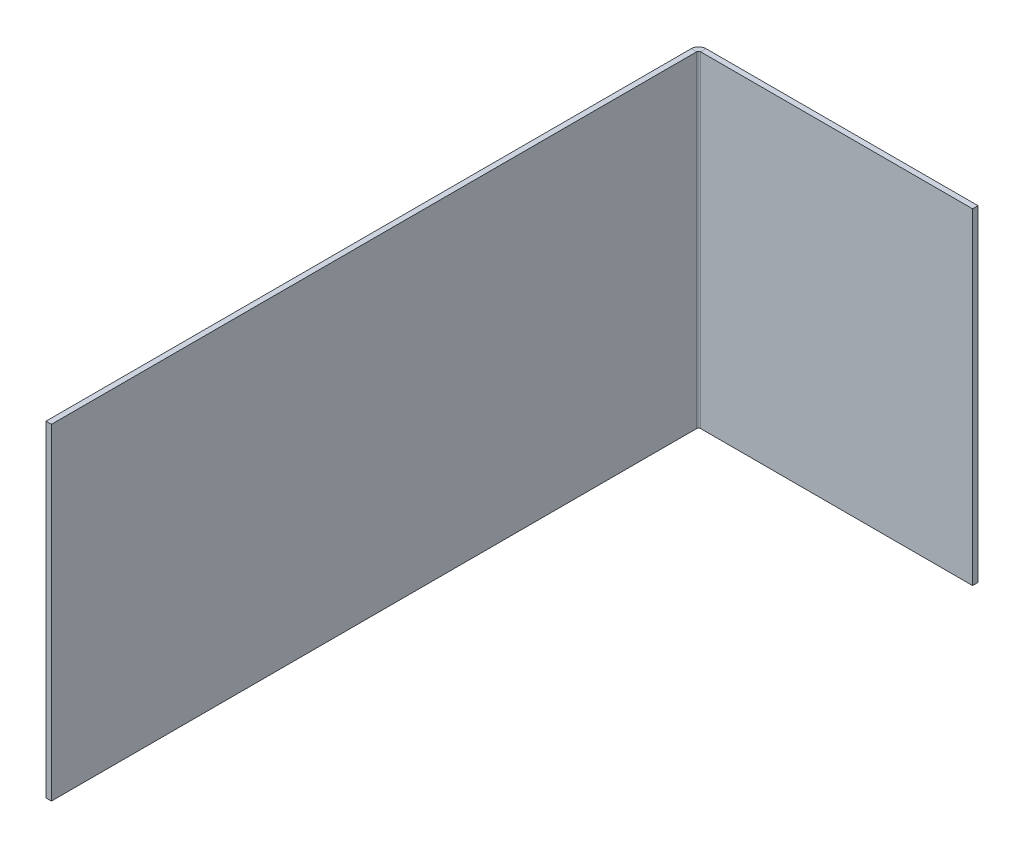
SolidWorks part; units mm, degrees
note: The reader was unsure of these and kept them because the rebuilt part matched: flange length of "Edge-Flange1".
material "1.0037 (S235JR)"
ref_plane "Front Plane" through (0, 0, 0) normal (0, 0, 1) x (1, 0, 0)
ref_plane "Top Plane" through (0, 0, 0) normal (0, 1, 0) x (1, 0, 0)
ref_plane "Right Plane" through (0, 0, 0) normal (1, 0, 0) x (0, 0, -1)
sketch "Sketch2" plane through (0, 0, 0) normal (0, 0, 1) x (1, 0, 0)
  line L1 (-50, 60) -> (50, 60)
  line L2 (-50, 60) -> (-50, -60)
  line L3 (-50, -60) -> (50, -60)
  line L4 (50, 60) -> (50, -60)
  line L5 (-50, 60) -> (50, -60) construction
  line L6 (-50, -60) -> (50, 60) construction
  point P0 (0, 0)
  dimension "D1" = 100
  dimension "D2" = 120
base flange "Base-Flange1" sketch "Sketch2" thickness 2 reverse thickness direction no parameters "D1"=0.7366
edge flange "Edge-Flange1" sketch "Sketch9" flange angle 90 flange length 240 flange position bend outside bend radius 0.7366 thickness 2 relief rectangular parameters "D6"=10
sketch "Sketch9" plane through (-50, 0, 0) normal (1, 0, 0) x (0, 1, 0)
  line L2 (-60, 0) -> (-60, 238)
  line L3 (-60, 238) -> (60, 238)
  line L4 (60, 238) -> (60, 0)
  line L5 (60, 0) -> (-60, 0) construction
  line L6 (60, 0) -> (-60, 0)
bend "EdgeBend1" bend radius 0.7366 bend angle 90 parameters "D5"=1
sketch "Bend-Lines1" [suppressed] plane through (0, 0, 0) normal (0, 1, 0) x (1, 0, 0)
sketch "Bounding-Box1" [suppressed] plane through (0, 0, 0) normal (0, 1, 0) x (1, 0, 0)
sheet metal parameters "Sheet-Metal1" thickness 2 parameters "D1"=0.7366
flat pattern "Flat-Pattern1" [suppressed]
sketch "Bend-Lines2" plane through (0, 0, 0) normal (0, 1, 0) x (1, 0, 0)
sketch "Bounding-Box2" [suppressed] plane through (0, 0, 0) normal (0, 1, 0) x (1, 0, 0)
sheet metal parameters "Sheet-Metal2" thickness 2 parameters "D1"=0.7366
flat pattern "Flat-Pattern1"
sketch "Bend-Lines2" plane through (0, 0, 0) normal (0, 0, 1) x (1, 0, 0)
  line L0 (-51.3639, 60) -> (-51.3639, -60) construction
  line L1 (-51.3639, 60) -> (-51.3639, -60) construction
sketch3d "Bounding-Box2" [suppressed]
  line L0 (-289.9912, -60, 0) -> (50, -60, 0) construction
  line L1 (-289.9912, 60, 0) -> (50, 60, 0) construction
  line L2 (-289.9912, -60, 0) -> (-289.9912, 60, 0) construction
  line L3 (50, -60, 0) -> (50, 60, 0) construction
bend of the flat pattern "Flatten-<EdgeBend1>1"
